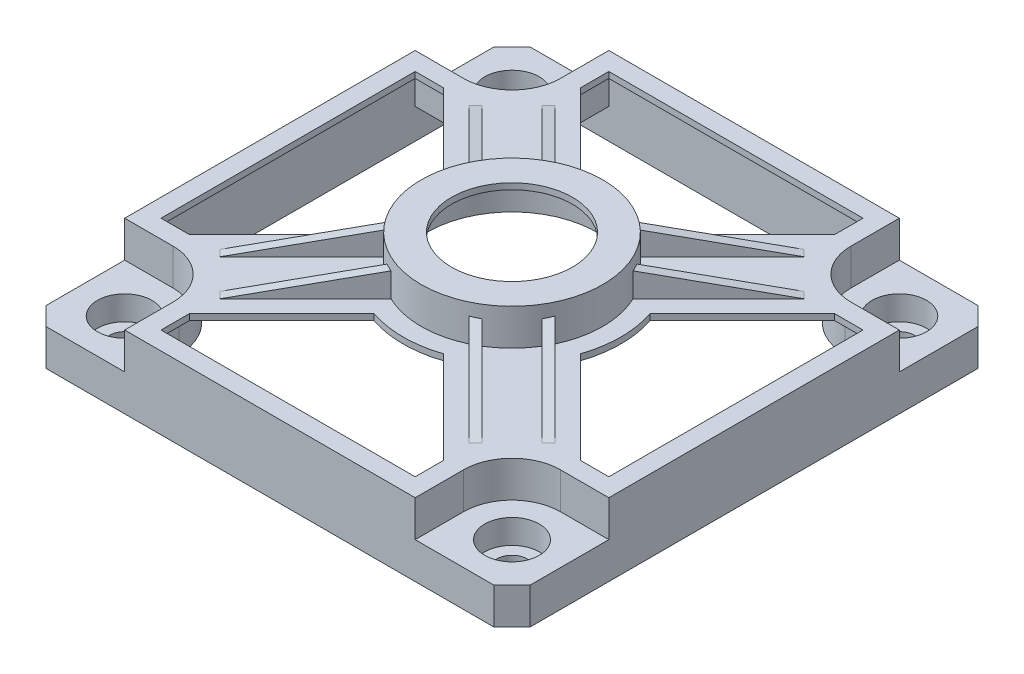
SolidWorks part; units mm, degrees
note: The reader was unsure of these and kept them because the rebuilt part matched: shared geometry of "Sketch1<4>", "Sketch1<5>".
ref_plane "Front Plane" through (0, 0, 0) normal (0, 0, 1) x (1, 0, 0)
ref_plane "Top Plane" through (0, 0, 0) normal (0, 1, 0) x (1, 0, 0)
ref_plane "Right Plane" through (0, 0, 0) normal (1, 0, 0) x (0, 0, -1)
sketch "Sketch1" plane through (0, 0, 0) normal (0, 1, 0) x (1, 0, 0)
  line L0 (-24, 40) -> (-24, 32)
  line L1 (40, -40) -> (-40, -40)
  line L2 (40, -40) -> (40, 40)
  line L3 (40, 40) -> (-40, 40)
  line L4 (-40, -40) -> (-40, 40)
  line L5 (40, -40) -> (-40, 40) construction
  line L6 (40, 40) -> (-40, -40) construction
  line L7 (-32, 24) -> (-40, 24)
  line L8 (24, 32) -> (24, 40)
  line L9 (40, 24) -> (32, 24)
  line L10 (32, -24) -> (40, -24)
  line L11 (24, -40) -> (24, -32)
  line L12 (-24, -32) -> (-24, -40)
  line L13 (-40, -24) -> (-32, -24)
  arc A0 (-24, 32) -> (-32, 24) centre (-32, 32) cw
  arc A1 (32, 24) -> (24, 32) centre (32, 32) cw
  arc A2 (24, -32) -> (32, -24) centre (32, -32) cw
  arc A3 (-32, -24) -> (-24, -32) centre (-32, -32) cw
  circle A4 centre (-32, 32) radius 2.5
  circle A5 centre (-32, 32) radius 4.5
  circle A6 centre (32, 32) radius 4.5
  circle A7 centre (32, 32) radius 2.5
  circle A8 centre (32, -32) radius 4.5
  circle A9 centre (32, -32) radius 2.5
  circle A10 centre (-32, -32) radius 4.5
  circle A11 centre (-32, -32) radius 2.5
  circle A12 centre (-32, 32) radius 3.5
  circle A13 centre (32, 32) radius 3.5
  circle A14 centre (32, -32) radius 3.5
  circle A15 centre (-32, -32) radius 3.5
  circle A16 centre (0, 0) radius 10
  point P0 (0, 0)
  point P29 (0, 0)
  point P41 (0, 0)
  point P49 (0, 0)
  dimension "D5" = 8
  dimension "D9" = 5
  dimension "D10" = 9
  dimension "D12" = 7
  dimension "D14" = 20
  dimension "D3" = 16
  dimension "D2" = 80
  dimension "D15" = 80
  dimension "D4" = 16
  dimension "D7" = 16
  dimension "D8" = 16
  dimension "D6" = 4
  dimension "D11" = 4
  dimension "D13" = 4
extrude "Boss-Extrude1" add sketch "Sketch1" along normal blind 12 contours L13 A3 L12 L1 L11 A2 L10 L2 L9 A1 L8 L3 L0 A0 L7 L4 A16
sketch "Sketch2" plane through (0, 12, 0) normal (0, 1, 0) x (1, 0, 0)
  circle A0 centre (0, 0) radius 15
  circle A1 centre (0, 0) radius 10 construction
  circle A2 centre (0, 0) radius 10
  dimension "D1" = 30
extrude "Boss-Extrude2" add sketch "Sketch2" along normal blind 6
sketch "Sketch3" plane through (0, 12, 0) normal (0, 1, 0) x (1, 0, 0)
  line L0 (40, -40) -> (-40, 40) construction
  line L1 (24, -40) -> (24, -32) construction
  line L3 (21, -37) -> (-21, -37)
  line L4 (21, -37) -> (21, -32.3137)
  line L5 (21, -32.3137) -> (5.7449, -17.0586)
  line L7 (0, 0) -> (0, -32.8883) construction
  line L8 (-21, -37) -> (-21, -32.3137)
  line L9 (-21, -32.3137) -> (-5.7449, -17.0586)
  line L10 (24, -40) -> (-24, -40) construction
  arc A0 (-5.7449, -17.0586) -> (5.7449, -17.0586) centre (0, 0) ccw
  circle A2 centre (0, 0) radius 15 construction
  dimension "D4" = 8
  dimension "D3" = 3
extrude "Cut-Extrude1" cut sketch "Sketch3" against normal through all
pattern_circular "CirPattern1" count 4 over 360 about axis through (0, 0, 0) along (0, 1, 0) of "Cut-Extrude1"
extrude "Boss-Extrude3" add sketch "Sketch1<4>" along normal blind 6 contours A0 L0 L3 L4 L7 A5
sketch "Sketch1<4>" plane through (0, 0, 0) normal (0, 1, 0) x (1, 0, 0) same geometry as "Sketch1"
extrude "Boss-Extrude4" add sketch "Sketch1<5>" along normal blind 2 contours A5 A12 | A12 A4 | A4
sketch "Sketch1<5>" plane through (0, 0, 0) normal (0, 1, 0) x (1, 0, 0) same geometry as "Sketch1"
pattern_circular "CirPattern2" count 4 over 360 about axis through (0, 0, 0) along (0, 1, 0) of "Boss-Extrude4", "Boss-Extrude3"
chamfer "Chamfer3" distance 3 angle 45 4 edges at (-40, 3, 40) (40, 3, 40) (40, 3, -40) (-40, 3, -40)
shell "Shell1" thickness 1
sketch "Sketch9" plane through (0, 0, 0) normal (0, -1, 0) x (1, 0, 0)
  line L5 (22, 38) -> (-22, 38)
  line L6 (-22, 38) -> (-22, 31.8995)
  line L7 (-22, 31.8995) -> (-6.0047, 15.9042)
  line L8 (6.0047, 15.9042) -> (22, 31.8995)
  line L9 (22, 31.8995) -> (22, 38)
  line L10 (22, 38) -> (-22, 38)
  line L11 (-22, 38) -> (-22, 31.8995)
  line L12 (-22, 31.8995) -> (-6.0047, 15.9042)
  line L13 (6.0047, 15.9042) -> (22, 31.8995)
  line L14 (22, 31.8995) -> (22, 38)
  line L15 (-38, 22) -> (-38, -22)
  line L16 (-38, -22) -> (-31.8995, -22)
  line L17 (-31.8995, -22) -> (-15.9042, -6.0047)
  line L18 (-15.9042, 6.0047) -> (-31.8995, 22)
  line L19 (-31.8995, 22) -> (-38, 22)
  line L20 (-38, 22) -> (-38, -22)
  line L21 (-38, -22) -> (-31.8995, -22)
  line L22 (-31.8995, -22) -> (-15.9042, -6.0047)
  line L23 (-15.9042, 6.0047) -> (-31.8995, 22)
  line L24 (-31.8995, 22) -> (-38, 22)
  line L25 (-22, -38) -> (22, -38)
  line L26 (22, -38) -> (22, -31.8995)
  line L27 (22, -31.8995) -> (6.0047, -15.9042)
  line L28 (-6.0047, -15.9042) -> (-22, -31.8995)
  line L29 (-22, -31.8995) -> (-22, -38)
  line L30 (-22, -38) -> (22, -38)
  line L31 (22, -38) -> (22, -31.8995)
  line L32 (22, -31.8995) -> (6.0047, -15.9042)
  line L33 (-6.0047, -15.9042) -> (-22, -31.8995)
  line L34 (-22, -31.8995) -> (-22, -38)
  line L35 (38, -22) -> (38, 22)
  line L36 (38, 22) -> (31.8995, 22)
  line L37 (31.8995, 22) -> (15.9042, 6.0047)
  line L38 (15.9042, -6.0047) -> (31.8995, -22)
  line L39 (31.8995, -22) -> (38, -22)
  line L40 (38, -22) -> (38, 22)
  line L41 (38, 22) -> (31.8995, 22)
  line L42 (31.8995, 22) -> (15.9042, 6.0047)
  line L43 (15.9042, -6.0047) -> (31.8995, -22)
  line L44 (31.8995, -22) -> (38, -22)
  arc A1 (6.0047, 15.9042) -> (-6.0047, 15.9042) centre (0, 0) ccw
  arc A2 (6.0047, 15.9042) -> (-6.0047, 15.9042) centre (0, 0) ccw
  arc A3 (-15.9042, 6.0047) -> (-15.9042, -6.0047) centre (0, 0) ccw
  arc A4 (-15.9042, 6.0047) -> (-15.9042, -6.0047) centre (0, 0) ccw
  arc A5 (-6.0047, -15.9042) -> (6.0047, -15.9042) centre (0, 0) ccw
  arc A6 (-6.0047, -15.9042) -> (6.0047, -15.9042) centre (0, 0) ccw
  arc A7 (15.9042, -6.0047) -> (15.9042, 6.0047) centre (0, 0) ccw
  arc A8 (15.9042, -6.0047) -> (15.9042, 6.0047) centre (0, 0) ccw
  circle A9 centre (0, 0) radius 11
  circle A10 centre (0, 0) radius 11
  dimension "D1" = 0
  dimension "D2" = 0
  dimension "D3" = 0
  dimension "D4" = 0
  dimension "D5" = 0
extrude "Cut-Extrude3" cut sketch "Sketch9" against normal up to surface (11 mm away) up to face at (0, 11, -28.7839)
sketch "Sketch10" plane through (0, 11, 0) normal (0, -1, 0) x (1, 0, 0)
  circle A1 centre (0, 0) radius 11
  circle A2 centre (0, 0) radius 11
  dimension "D1" = 0
extrude "Cut-Extrude4" cut sketch "Sketch10" against normal up to surface (6 mm away) up to face at (0, 17, 14)
sketch "Sketch12" plane through (0, 12, 0) normal (0, 1, 0) x (1, 0, 0)
  line L0 (-6.4645, -13.5355) -> (-20.6066, -27.6777)
  line L1 (-5.7449, -17.0586) -> (-21, -32.3137) construction
  line L2 (-7.839, -12.7887) -> (-21.6673, -26.617)
  line L3 (-20.6066, -27.6777) -> (-21.6673, -26.617)
  line L4 (-7.5251, -12.4749) -> (-21.6673, -26.617) construction
  line L5 (-13.5355, -6.4645) -> (-27.6777, -20.6066)
  line L6 (-27.6777, -20.6066) -> (-26.617, -21.6673)
  line L7 (-26.617, -21.6673) -> (-12.7887, -7.839)
  circle A0 centre (0, 0) radius 15 construction
  arc A1 (-13.5355, -6.4645) -> (-12.7887, -7.839) centre (0, 0) ccw
  arc A2 (-7.839, -12.7887) -> (-6.4645, -13.5355) centre (0, 0) ccw
  dimension "D2" = 20
  dimension "D4" = 10
  dimension "D5" = 1.5
  dimension "D3" = 1.5
extrude "Boss-Extrude5" add sketch "Sketch12" along normal blind 6 separate body
ref_plane "Plane3" through (0, 0, 0) normal (0.7071, 0, 0.7071) x (0.7071, 0, -0.7071)
sketch "Sketch14" plane through (0, 0, 0) normal (0.7071, 0, 0.7071) x (0.7071, 0, -0.7071)
  line L0 (-14.1421, 16) -> (-34.1421, 12)
  line L5 (-34.1421, 12) -> (-14.1421, 12)
  line L6 (-14.1421, 12) -> (-14.1421, 16)
  line L7 (-34.1421, 12) -> (-14.1421, 12) construction
  line L9 (-14.1421, 18) -> (-14.1421, 12) construction
  line L10 (-34.1421, 18) -> (-34.1421, 12) construction
  dimension "D1" = 4
extrude "Cut-Extrude7" cut sketch "Sketch14" against normal through all both and the other way through all flip side to cut
pattern_circular "CirPattern5" count 4 over 360 about axis through (0, 0, 0) along (0, 1, 0) of bodies 119 118
sketch "Sketch15" plane through (0, 2, 0) normal (0, 1, 0) x (1, 0, 0)
  circle A0 centre (-32, -32) radius 2.5
  circle A1 centre (-32, 32) radius 2.5
  circle A2 centre (32, 32) radius 2.5
  circle A3 centre (32, -32) radius 2.5
  circle A4 centre (-32, -32) radius 4.5 construction
  point P12 (0, 0)
  dimension "D1" = 5
  dimension "D3" = 32
  dimension "D4" = 64
  dimension "D2" = 4
extrude "Cut-Extrude8" cut sketch "Sketch15" against normal through all both and the other way through all
combine bodies "Combine1" bodies to combine 124 122 119 120 125 118 123 126 121
equation "\"a\"= 12"
equation "\"b\"= 20"
equation "\"c\"= 16"
equation "\"d\"= 80"
equation "\"e\"= 30"
equation "\"f\"= 1.5"
equation "\"g\"= 3"
equation "\"t\"= 1"
equation "\"D3@Sketch12\"=\"f\""
equation "\"D2@Sketch12\"=\"b\""
equation "\"D1@Shell1\"=\"t\""
equation "\"D2@Sketch1\"=\"d\""
equation "\"D15@Sketch1\"=\"d\""
equation "\"D8@Sketch1\"=\"c\""
equation "\"D7@Sketch1\"=\"c\""
equation "\"D4@Sketch1\"=\"c\""
equation "\"D1@Sketch2\"=\"e\""
equation "\"D1@Sketch12\"=\"g\""
equation "\"D5@Sketch12\"=\"f\""
equation "\"D3@Sketch3\"=\"g\""
equation "\"D2@Sketch3\"=\"g\""
equation "\"D1@Sketch3\"=\"g\""
